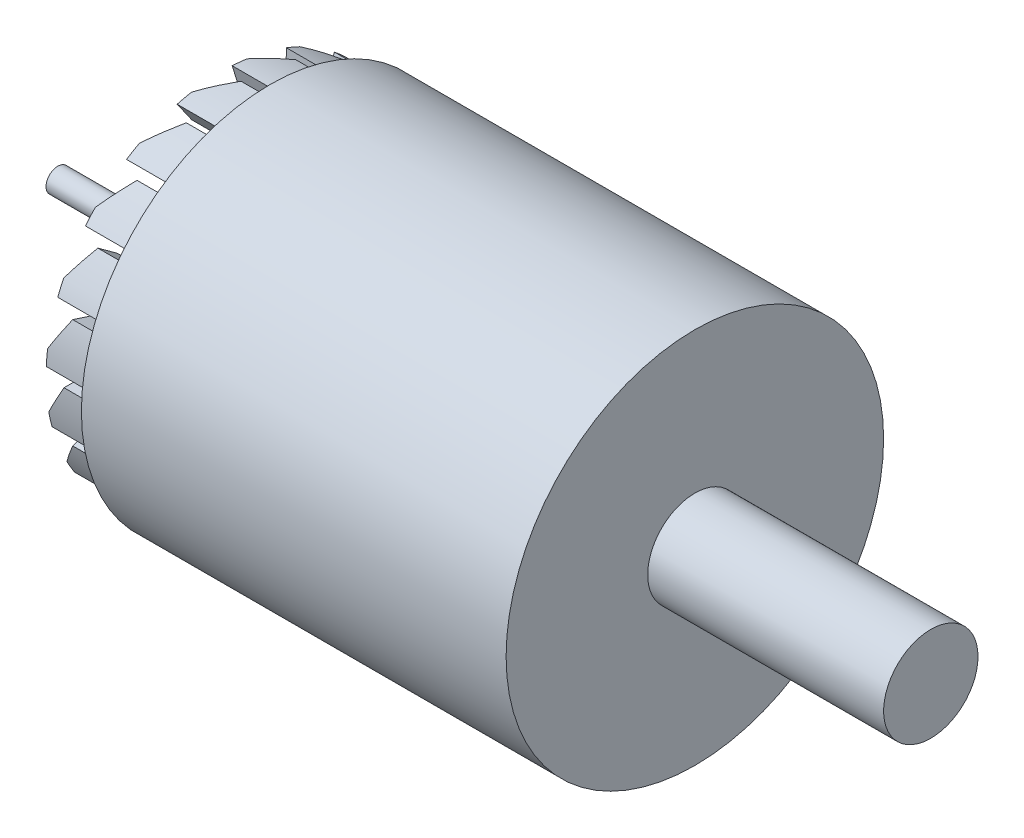
SolidWorks part; units mm, degrees
material "ABS"
ref_plane "Front Plane" through (0, 0, 0) normal (0, 0, 1) x (1, 0, 0)
ref_plane "Top Plane" through (0, 0, 0) normal (0, 1, 0) x (1, 0, 0)
ref_plane "Right Plane" through (0, 0, 0) normal (1, 0, 0) x (0, 0, -1)
sketch "Sketch3" plane through (0, 0, 0) normal (1, 0, 0) x (0, 0, -1)
  circle A0 centre (0, 0) radius 8
  dimension "D1" = 16
extrude "Boss-Extrude2" add sketch "Sketch3" along normal mid plane 18
sketch "Sketch4" plane through (9, 0, 0) normal (1, 0, 0) x (0, 0, -1)
  circle A0 centre (0, 0) radius 2
  dimension "D1" = 4
sketch "Sketch5" plane through (-9, 0, 0) normal (-1, 0, 0) x (0, 0, 1)
  circle A0 centre (0, 0) radius 0.5
  dimension "D1" = 1
extrude "Boss-Extrude4" add sketch "Sketch5" along normal blind 9
sketch "Sketch6" plane through (-9, 0, 0) normal (-1, 0, 0) x (0, 0, 1)
  line L0 (0, 0) -> (0, -7.5) construction
  line L1 (0, 0) -> (-1.9411, -7.2444) construction
  line L2 (0, -7.5) -> (0, -6.5)
  line L3 (-1.9411, -7.2444) -> (-1.6823, -6.2785)
  circle A0 centre (0, 0) radius 7.5 construction
  arc A1 (-1.6823, -6.2785) -> (0, -6.5) centre (0, 0) ccw
  arc A2 (-1.9411, -7.2444) -> (0, -7.5) centre (0, 0) ccw
  dimension "D1" = 15
  dimension "D2" = 13
  dimension "D3" = 15
extrude "Boss-Extrude6" add sketch "Sketch6" along normal blind 2 contours A1 L2 A2 L3
sketch "Sketch8" plane through (-11, 0, 0) normal (-1, 0, 0) x (0, 0, 1)
  line L0 (-1.9411, -7.2444) -> (-1.3244, -6.3636)
  line L1 (-1.9411, -7.2444) -> (-1.6823, -6.2785) construction
  line L2 (-1.9411, -7.2444) -> (-1.6823, -6.2785)
  line L3 (-1.6823, -6.2785) -> (-1.3244, -6.3636)
  arc A0 (-1.6823, -6.2785) -> (0, -6.5) centre (0, 0) ccw construction
  dimension "D1" = 20
extrude "Cut-Extrude6" cut sketch "Sketch8" against normal up to surface (2 mm away) contours L0 L3 L2 up to face at (-9, -6.9104, -0.9098)
sketch "Sketch10" plane through (-11, 0, 0) normal (-1, 0, 0) x (0, 0, 1)
  line L1 (-1.3244, -3.8636) -> (3.6756, -3.8636)
  line L2 (-1.3244, -3.8636) -> (-1.3244, -8.8636)
  line L3 (-1.3244, -8.8636) -> (3.6756, -8.8636)
  line L4 (3.6756, -3.8636) -> (3.6756, -8.8636)
  dimension "D1" = 5
  dimension "D2" = 5
extrude "Cut-Extrude10" cut sketch "Sketch10" against normal blind 1 draft 60 contours L4 L3 L2 L1
pattern_circular "CirPattern10" count 20 over 360 about axis through (-18, 0, 0) along (1, 0, 0) of face at (-10.0474, -7.3941, -1.0438) of face at (-11, -6.976, -1.6333) of face at (-10.5225, -6.8335, -0.4973) of face at (-9.4633, -6.4318, -0.6622) of face at (-9.75, -7.0242, -1.787) of face at (-9.6177, -7, 0)
extrude "Boss-Extrude7" add sketch "Sketch4" along normal blind 10
